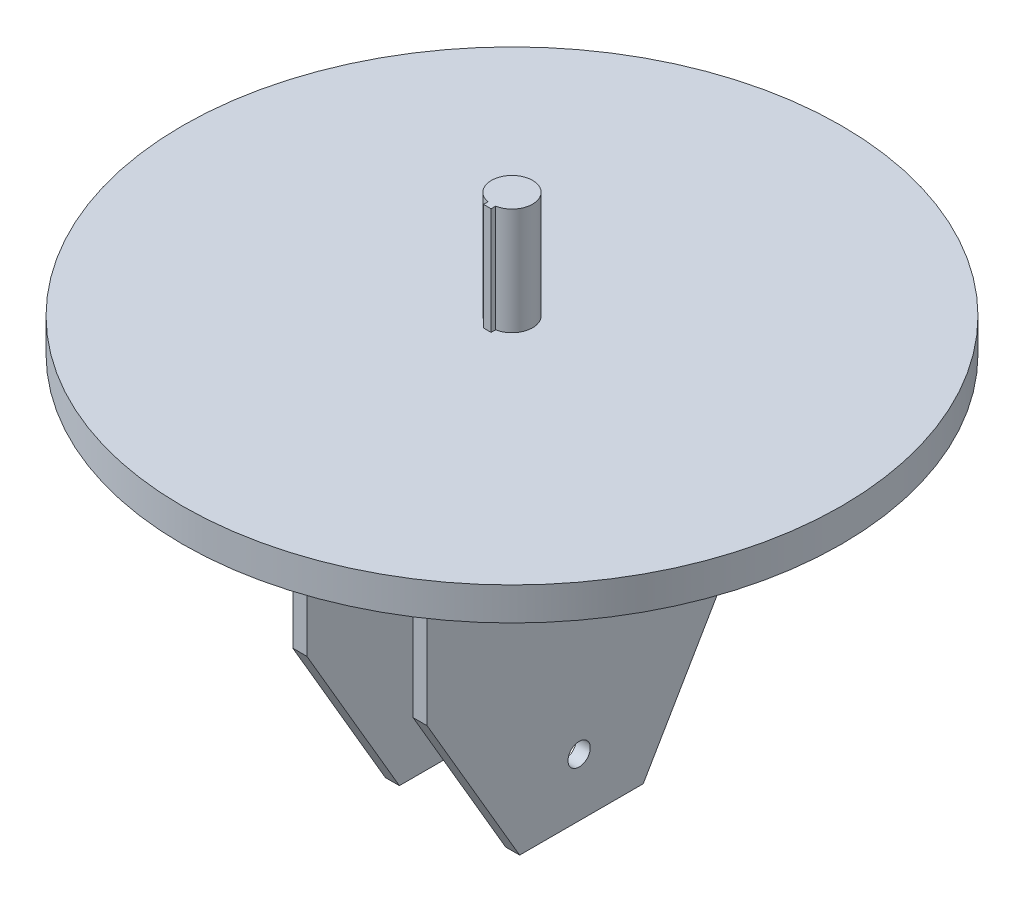
SolidWorks part; units mm, degrees
ref_plane "Front Plane" through (0, 0, 0) normal (0, 0, 1) x (1, 0, 0)
ref_plane "Top Plane" through (0, 0, 0) normal (0, 1, 0) x (1, 0, 0)
ref_plane "Right Plane" through (0, 0, 0) normal (1, 0, 0) x (0, 0, -1)
sketch "Sketch1" plane through (0, 0, 0) normal (0, 1, 0) x (1, 0, 0)
  circle A0 centre (0, 0) radius 400
  dimension "D1" = 800
extrude "Boss-Extrude1" add sketch "Sketch1" along normal blind 10
sketch "Sketch3" plane through (0, 10, 0) normal (0, 1, 0) x (1, 0, 0)
  line L5 (-4.6, -30.015) -> (4.6, -30.015)
  line L6 (-4.6, -30.015) -> (-4.6, -24.5732)
  line L8 (4.6, -30.015) -> (4.6, -24.5732)
  line L9 (-4.6, -30.015) -> (0, -25) construction
  line L10 (0, -25) -> (4.6, -30.015) construction
  arc A0 (4.6, -24.5732) -> (-4.6, -24.5732) centre (0, 0) ccw
  point P3 (0, -25)
  dimension "D1" = 50
extrude "Boss-Extrude5" add sketch "Sketch3" along normal blind 130
extrude "Boss-Extrude6" add sketch "Sketch1<4>" against normal blind 30
sketch "Sketch1<4>" plane through (0, 0, 0) normal (0, 1, 0) x (1, 0, 0) same geometry as "Sketch1"
sketch "Sketch4" plane through (0, -30, 0) normal (0, -1, 0) x (1, 0, 0)
  line L7 (-81.5, 184.5559) -> (-64.5, 184.5559)
  line L8 (-81.5, 184.5559) -> (-81.5, -184.6467)
  line L9 (-81.5, -184.6467) -> (-64.5, -184.6467)
  line L10 (-64.5, 184.5559) -> (-64.5, -184.6467)
  line L11 (81.5, 184.5559) -> (64.5, 184.5559)
  line L12 (81.5, 184.5559) -> (81.5, -190.1338)
  line L13 (81.5, -190.1338) -> (64.5, -190.1338)
  line L14 (64.5, 184.5559) -> (64.5, -190.1338)
  dimension "D1" = 17
  dimension "D2" = 17
  dimension "D3" = 81.5
  dimension "D4" = 81.5
extrude "Boss-Extrude7" add sketch "Sketch4" along normal blind 450
sketch "Sketch5" plane through (81.5, 0, 0) normal (1, 0, 0) x (0, 0, -1)
  line L0 (-184.5559, -287.7706) -> (-72.211, -480)
  line L1 (-184.5559, -480) -> (-184.5559, -30) construction
  line L2 (190.1338, -480) -> (-184.5559, -480) construction
  line L3 (-72.211, -480) -> (-184.5559, -480)
  line L4 (-184.5559, -480) -> (-184.5559, -287.7706)
  line L5 (77.789, -480) -> (190.1338, -287.7706)
  line L6 (190.1338, -480) -> (190.1338, -30) construction
  line L7 (190.1338, -287.7706) -> (190.1338, -480)
  line L8 (190.1338, -480) -> (77.789, -480)
  dimension "D1" = 150
extrude "Cut-Extrude1" cut sketch "Sketch5" against normal blind 300 and the other way through all
sketch "Sketch6" plane through (-81.5, 0, 0) normal (-1, 0, 0) x (0, 0, 1)
  line L0 (72.211, -480) -> (-77.789, -480) construction
  circle A0 centre (0, -410) radius 13.5
  dimension "D1" = 27
  dimension "D2" = 70
extrude "Cut-Extrude2" cut sketch "Sketch6" against normal blind 300
